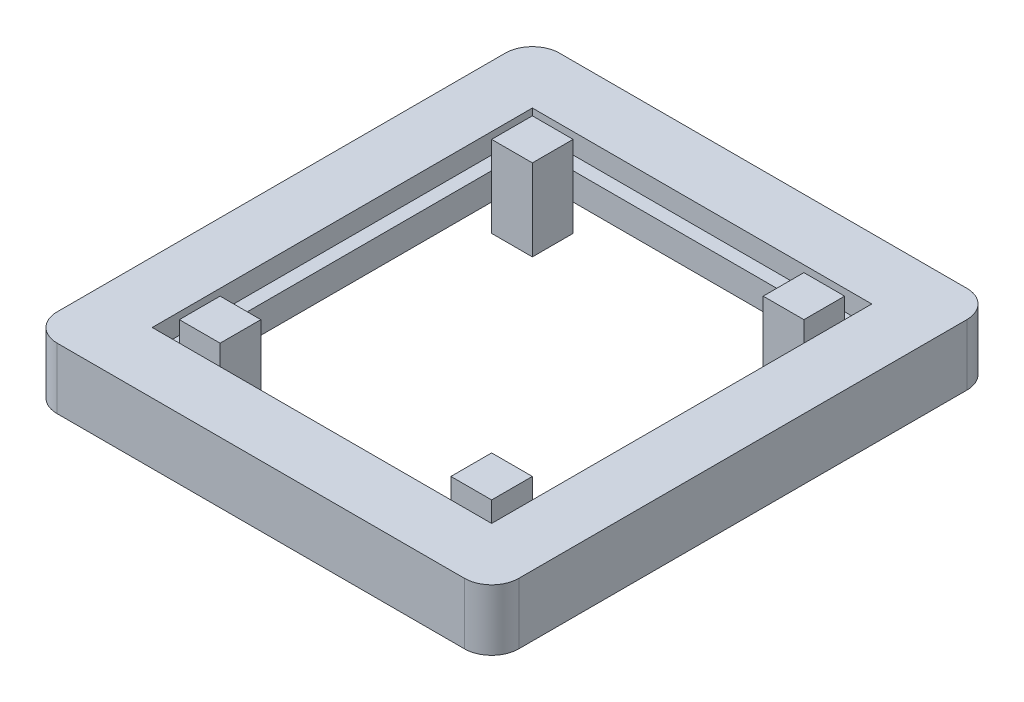
SolidWorks part; units mm, degrees
ref_plane "Front Plane" through (0, 0, 0) normal (0, 0, 1) x (1, 0, 0)
ref_plane "Top Plane" through (0, 0, 0) normal (0, 1, 0) x (1, 0, 0)
ref_plane "Right Plane" through (0, 0, 0) normal (1, 0, 0) x (0, 0, -1)
sketch "Sketch1" plane through (0, 0, 0) normal (0, 1, 0) x (1, 0, 0)
  line L0 (-292.1, 330.2) -> (292.1, 330.2)
  line L1 (-317.5, 355.6) -> (317.5, 355.6)
  line L2 (-317.5, 355.6) -> (-317.5, -355.6)
  line L3 (-317.5, -355.6) -> (317.5, -355.6)
  line L4 (317.5, 355.6) -> (317.5, -355.6)
  line L5 (-317.5, 355.6) -> (317.5, -355.6) construction
  line L6 (-317.5, -355.6) -> (317.5, 355.6) construction
  line L7 (292.1, 330.2) -> (292.1, -330.2)
  line L8 (-292.1, -330.2) -> (292.1, -330.2)
  line L9 (-292.1, 330.2) -> (-292.1, -330.2)
  line L13 (-292.1, 254) -> (-215.9, 254)
  line L14 (-215.9, 330.2) -> (-215.9, 254)
  line L27 (292.1, 330.2) -> (215.9, 330.2)
  line L28 (292.1, 330.2) -> (292.1, 254)
  line L29 (292.1, 254) -> (215.9, 254)
  line L30 (215.9, 330.2) -> (215.9, 254)
  line L31 (-292.1, -330.2) -> (-215.9, -330.2)
  line L32 (-292.1, -330.2) -> (-292.1, -254)
  line L33 (-292.1, -254) -> (-215.9, -254)
  line L34 (-215.9, -330.2) -> (-215.9, -254)
  line L35 (292.1, -330.2) -> (215.9, -330.2)
  line L36 (292.1, -330.2) -> (292.1, -254)
  line L37 (292.1, -254) -> (215.9, -254)
  line L38 (215.9, -330.2) -> (215.9, -254)
  point P0 (0, 0)
  dimension "D1" = 635
  dimension "D2" = 711.2
  dimension "D4" = 101.6
  dimension "D5" = 101.6
  dimension "D6" = 101.6
  dimension "D3" = 25.4
extrude "Boss-Extrude2" add sketch "Sketch1" along normal blind 50.8 contours L4 L1 L2 L3 L9 L0 L7 L8 region at (0, 0, -346.0657)
extrude "Boss-Extrude3" add sketch "Sketch1<3>" along normal blind 101.6 and the other way blind 50.8 contours L14 L0 L9 L13 | L0 L30 L29 L7 | L38 L8 L7 L37 | L8 L34 L33 L9 region at (-254, 0, -292.1) region at (254, 0, -292.1) region at (-254, 0, 292.1) region at (254, 0, 292.1)
sketch "Sketch1<3>" plane through (0, 0, 0) normal (0, 1, 0) x (1, 0, 0) same geometry as "Sketch1"
sketch "Sketch3" plane through (0, 0, 0) normal (0, 1, 0) x (1, 0, 0)
  line L10 (-317.5, -355.6) -> (317.5, -355.6) construction
  line L11 (317.5, 355.6) -> (317.5, -355.6) construction
  line L12 (-317.5, 355.6) -> (317.5, 355.6) construction
  line L13 (-317.5, 355.6) -> (-317.5, -355.6) construction
  line L14 (-431.8, -469.9) -> (431.8, -469.9)
  line L15 (431.8, -469.9) -> (431.8, 469.9)
  line L16 (-431.8, 469.9) -> (-431.8, -469.9)
  line L17 (431.8, 469.9) -> (-431.8, 469.9)
  line L18 (-431.8, -469.9) -> (431.8, -469.9)
  line L19 (431.8, -469.9) -> (431.8, 469.9)
  line L20 (-431.8, 469.9) -> (-431.8, -469.9)
  line L21 (431.8, 469.9) -> (-431.8, 469.9)
  line L22 (-317.5, -355.6) -> (317.5, -355.6)
  line L23 (317.5, 355.6) -> (317.5, -355.6)
  line L24 (-317.5, 355.6) -> (317.5, 355.6)
  line L25 (-317.5, 355.6) -> (-317.5, -355.6)
  dimension "D1" = 114.3
extrude "Boss-Extrude4" add sketch "Sketch3" along normal offset from surface 139.7 and the other way blind 25.4 up to face at (-254, -50.8, 292.1)
fillet "Fillet1" radius 50.8 4 edges at (431.8, 31.75, 469.9) (-431.8, 31.75, 469.9) (-431.8, 31.75, -469.9) (431.8, 31.75, -469.9)
